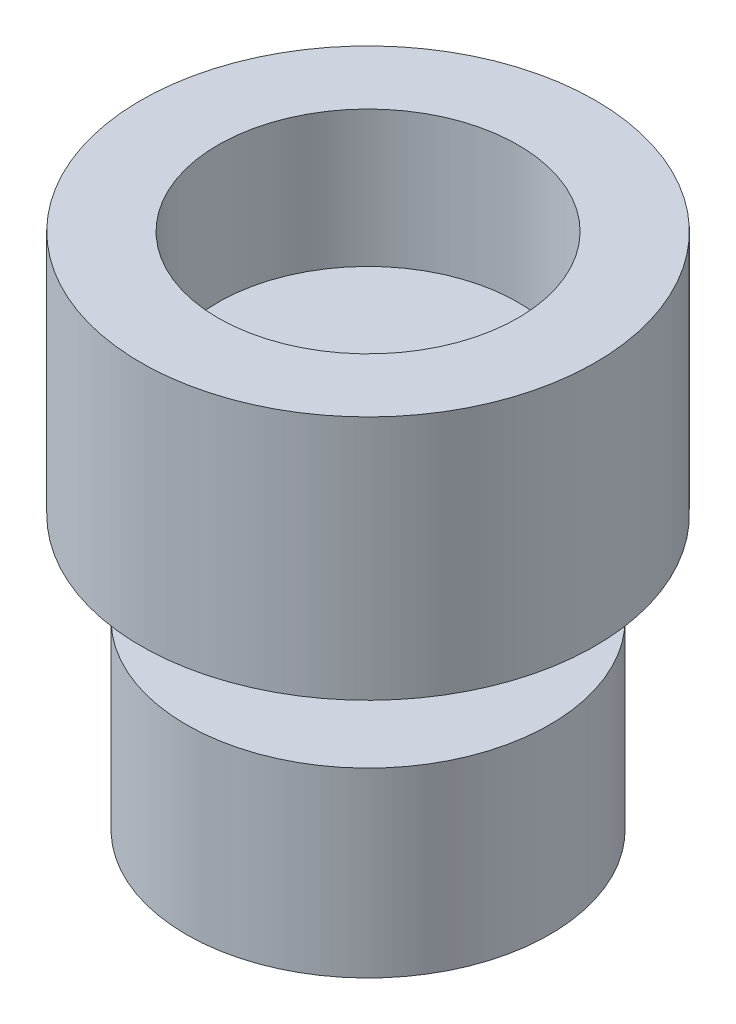
SolidWorks part; units mm, degrees
ref_plane "Front Plane" through (0, 0, 0) normal (0, 0, 1) x (1, 0, 0)
ref_plane "Top Plane" through (0, 0, 0) normal (0, 1, 0) x (1, 0, 0)
ref_plane "Right Plane" through (0, 0, 0) normal (1, 0, 0) x (0, 0, -1)
sketch "Sketch1" plane through (0, 0, 0) normal (0, 1, 0) x (1, 0, 0)
  circle A0 centre (-0.522, 0.5111) radius 2
  circle A1 centre (-0.522, 0.5111) radius 2.5
  dimension "D1" = 4
  dimension "D2" = 5
extrude "Boss-Extrude1" add sketch "Sketch1" along normal blind 2.7 contours A1
extrude "Boss-Extrude2" add sketch "Sketch1<3>" along normal blind 1 contours A0 region at (-0.522, 0, -0.5111)
sketch "Sketch1<3>" plane through (0, 0, 0) normal (0, 1, 0) x (1, 0, 0) same geometry as "Sketch1"
sketch "Sketch5" plane through (0, 0, 0) normal (0, -1, 0) x (1, 0, 0)
  circle A2 centre (-0.522, -0.5111) radius 1
  circle A3 centre (-0.522, -0.5111) radius 1
  dimension "D2" = 2
  dimension "D1" = 1.5
extrude "Boss-Extrude3" add sketch "Sketch5" along normal blind 1 contours A3
sketch "Sketch6" plane through (0, -1, 0) normal (0, -1, 0) x (1, 0, 0)
  circle A0 centre (-0.522, -0.5111) radius 2
  dimension "D1" = 4
extrude "Boss-Extrude4" add sketch "Sketch6" along normal blind 2
sketch "Sketch8" plane through (0, -3, 0) normal (0, -1, 0) x (-1, 0, 0)
  circle A0 centre (0.522, 0.5111) radius 1.5
  dimension "D1" = 3
sketch "Sketch11" plane through (0, 2.7, 0) normal (0, 1, 0) x (1, 0, 0)
  text T0 "VIII" font "Century Gothic" height in points 5
sketch "Sketch12" plane through (0, 2.7, 0) normal (0, 1, 0) x (1, 0, 0)
  circle A0 centre (-0.522, 0.5111) radius 1.65
extrude "Cut-Extrude1" cut sketch "Sketch12" against normal blind 1.5
